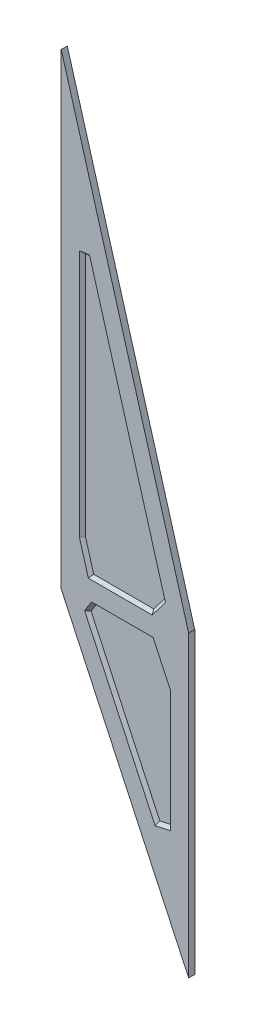
SolidWorks part; units mm, degrees
ref_plane "Plan de face" through (0, 0, 0) normal (0, 0, 1) x (1, 0, 0)
ref_plane "Plan de dessus" through (0, 0, 0) normal (0, 1, 0) x (1, 0, 0)
ref_plane "Plan de droite" through (0, 0, 0) normal (1, 0, 0) x (0, 0, -1)
sketch "Esquisse1" plane through (0, 0, 0) normal (0, 0, 1) x (1, 0, 0)
  line L0 (210, 769.9989) -> (0, 42.1417)
  line L1 (0, 42.1417) -> (0, 0)
  line L2 (0, 0) -> (210, 727.8571) construction
  line L3 (210, 727.8571) -> (210, 769.9989)
  line L4 (210, 769.9989) -> (209.579, 771.1189)
  line L5 (210, 727.8571) -> (210, 0)
  line L6 (210, 0) -> (0, 0) construction
  line L7 (0, 0) -> (0, -450)
  line L8 (0, -450) -> (210, 0)
  line L9 (210, 0) -> (210.5402, 0.5304)
  dimension "D1" = 210
  dimension "D2" = 769.9989
  dimension "D3" = 11.6821
  dimension "D4" = 450
extrude "Boss.-Extru.1" add sketch "Esquisse1" along normal blind 10 contours L7 L8 L5 L3 L0 L1 region at (112.7052, 112.1437, 0)
sketch "Esquisse2" plane through (0, 0, 10) normal (0, 0, 1) x (1, 0, 0)
  line L0 (60, 37.9004) -> (165.3026, 37.9004)
  line L1 (180, 88.8413) -> (180, 497.7984)
  line L2 (58.6117, 6.6555) -> (30, -54.6554)
  line L3 (160, 6.6555) -> (58.6117, 6.6555)
  line L4 (180, 497.7984) -> (163.3673, 500.1498)
  line L5 (55.3731, -260.4021) -> (30, -254.7731)
  line L6 (30, -54.6554) -> (30, -254.7731)
  line L7 (0, -450) -> (210, 0) construction
  line L8 (30, 37.9004) -> (30, -314.7731)
  line L9 (30, -314.7731) -> (180, 6.6555)
  line L10 (180, 6.6555) -> (180, 557.7984)
  line L11 (180, 557.7984) -> (30, 37.9004)
  line L12 (30, 37.9004) -> (30, -314.7731) construction
  line L13 (55.3731, -260.4021) -> (171.5423, -11.4682)
  line L14 (180, 6.6555) -> (180, 557.7984) construction
  line L15 (163.3673, 500.1498) -> (38.3163, 66.7247)
  line L16 (180, 88.8413) -> (165.3026, 37.9004)
  line L17 (210, 769.9989) -> (0, 42.1417) construction
  line L18 (38.3163, 66.7247) -> (60, 37.9004)
  line L19 (171.5423, -11.4682) -> (160, 6.6555)
  dimension "D2" = 160
  dimension "D3" = 140
  dimension "D1" = 30
extrude "Enlèv. mat.-Extru.1" cut sketch "Esquisse2" against normal blind 5
chamfer "Chanfrein1" distance 5 angle 45 12 edges at (165.7711, -2.4064, 5) (113.4577, -135.9351, 5) (42.6866, -257.5876, 5) (30, -154.7142, 5) (44.3059, -23.9999, 5) (109.3059, 6.6555, 5) (171.6837, 498.9741, 5) (180, 293.3199, 5) (172.6513, 63.3709, 5) (112.6513, 37.9004, 5) (49.1582, 52.3126, 5) (100.8418, 283.4373, 5)
mirror "Symétrie1" about plane through (0, 0, 10) normal (1, 0, 0) of bodies 102
sketch "Esquisse3" plane through (0, 0, 10) normal (0, 0, 1) x (1, 0, 0)
  line L1 (0, -450) -> (617.7813, -450)
  line L2 (0, -450) -> (0, 909.0733)
  line L3 (0, 909.0733) -> (617.7813, 909.0733)
  line L4 (617.7813, -450) -> (617.7813, 909.0733)
extrude "Enlèv. mat.-Extru.2" cut sketch "Esquisse3" against normal blind 10
